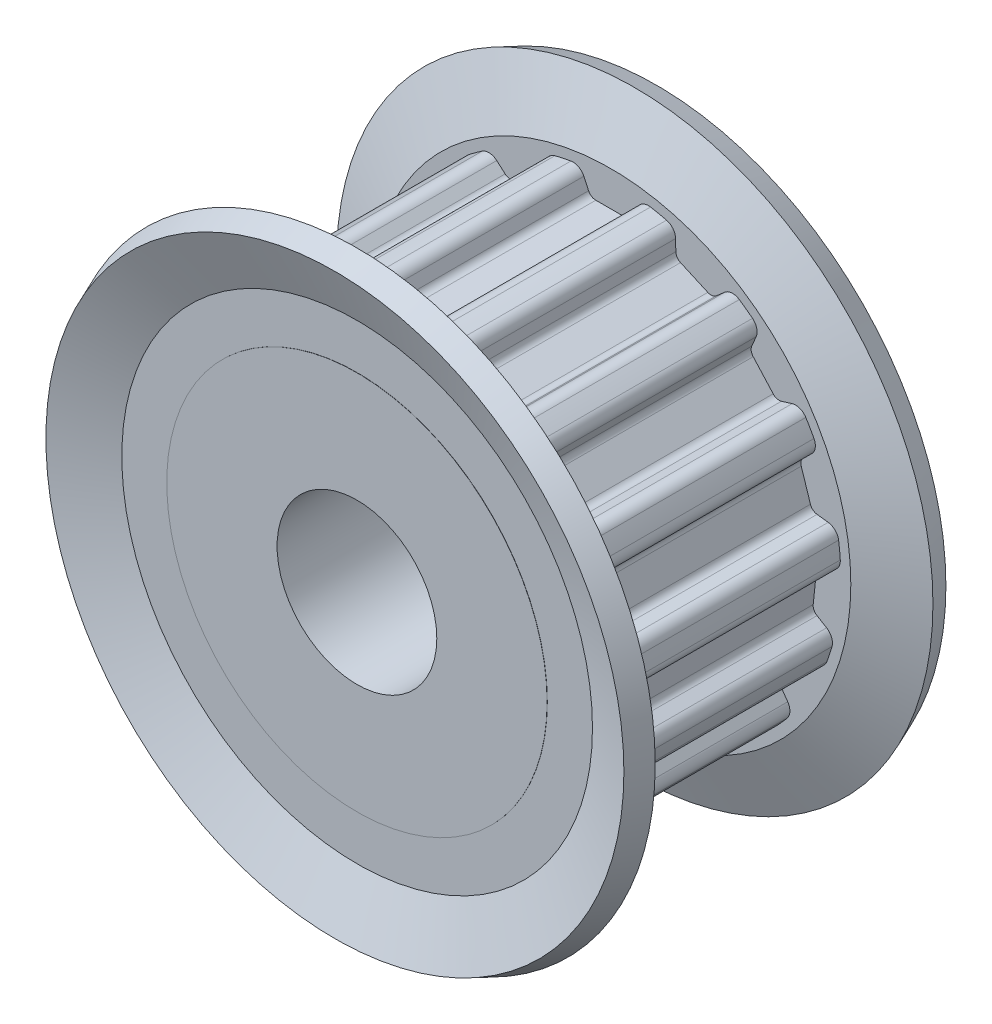
SolidWorks part; units mm, degrees
ref_plane "Front Plane" through (0, 0, 0) normal (0, 0, 1) x (1, 0, 0)
ref_plane "Top Plane" through (0, 0, 0) normal (0, 1, 0) x (1, 0, 0)
ref_plane "Right Plane" through (0, 0, 0) normal (1, 0, 0) x (0, 0, -1)
ref_axis "Axis1" through (0, 0, 73.2677) along (0, 0, -1)
sketch "SketchRevolveGearBelt01" plane through (0, 0, 0) normal (1, 0, 0) x (0, 0, -1)
  line L0 (0, 0) -> (1, 0) construction
  line L1 (6.96, 0) -> (6.96, 9.525)
  line L2 (6.96, 9.525) -> (6.95, 9.525)
  line L3 (6.95, 9.525) -> (6.95, 11.7863)
  line L4 (6.95, 11.7863) -> (8.0633, 14.4741)
  line L5 (8.0633, 14.4741) -> (6.9547, 14.9333)
  line L6 (6.9547, 14.9333) -> (5.75, 12.025)
  line L7 (5.75, 12.025) -> (5.75, 11.525)
  line L8 (5.75, 11.525) -> (-5.75, 11.525)
  line L9 (-5.75, 11.525) -> (-5.75, 12.025)
  line L10 (-5.75, 12.025) -> (-6.9547, 14.9333)
  line L11 (-6.9547, 14.9333) -> (-8.0633, 14.4741)
  line L12 (-8.0633, 14.4741) -> (-6.95, 11.7863)
  line L13 (-6.95, 11.7863) -> (-6.95, 9.525)
  line L14 (-6.95, 9.525) -> (-6.96, 9.525)
  line L15 (-6.96, 9.525) -> (-6.96, 0)
  line L16 (-6.96, 0) -> (6.96, 0)
  dimension "GearBeltSide1" = 6.96
  dimension "GearBeltFlange1OutsideWidth" = 6.95
  dimension "GearBeltFlange1OutsideLength" = 2.2613
  dimension "GearBeltFlange1X" = 1.1133
  dimension "GearBeltFlange1Y" = 2.6878
  dimension "GearBeltFlangeThickness" = 1.2
  dimension "GearBeltToothWidth1" = 5.75
  dimension "GearBeltFlangeInside" = 0.5
  dimension "GearBeltOutsideDiameter" = 11.525
  dimension "GearBeltToothWidth2" = 5.75
  dimension "GearBeltFlange2X" = 1.1133
  dimension "GearBeltFlange2OutsideWidth" = 6.95
revolve "GearBelt01" add sketch "SketchRevolveGearBelt01" angle 360 about L0
sketch "SketchToothGearBelt01" plane through (0, 0, 0) normal (0, 0, 1) x (1, 0, 0)
  line L0 (-1.3466, 11.0138) -> (-1.1098, 10.506)
  line L1 (-0.7473, 10.275) -> (0.7473, 10.275)
  line L2 (1.1098, 10.506) -> (1.3466, 11.0138)
  line L3 (1.9942, 11.3512) -> (0, 13.8912)
  line L4 (0, 13.8912) -> (-1.9942, 11.3512)
  arc A0 (-1.9942, 11.3512) -> (-1.3466, 11.0138) centre (-1.8904, 10.7602) cw
  arc A1 (-1.1098, 10.506) -> (-0.7473, 10.275) centre (-0.7473, 10.675) ccw
  arc A2 (0.7473, 10.275) -> (1.1098, 10.506) centre (0.7473, 10.675) ccw
  arc A3 (1.3466, 11.0138) -> (1.9942, 11.3512) centre (1.8904, 10.7602) cw
  dimension "GearBeltToothR1" = 1.2
  dimension "GearBeltToothR2" = 0.8
  dimension "GearBeltToothX1" = 0.2368
  dimension "GearBeltToothY1" = 0.5078
  dimension "GearBeltToothRootX" = 10.275
  dimension "GearBeltToothRootY" = 10.275
  dimension "GearBeltToothX2" = 0.2368
  dimension "GearBeltToothY2" = 0.5078
  dimension "GearBeltToothCapX1" = 1.9942
  dimension "GearBeltToothCapY1" = 2.54
  dimension "GearBeltToothCapX2" = 1.9942
  dimension "GearBeltToothCapY2" = 2.54
extrude "ToothExtrudeCutGearBelt01" cut sketch "SketchToothGearBelt01" against normal blind 5.75 and the other way blind 5.75
pattern_circular "PatternGearBelt01" count 15 every 24 about axis through (0, 0, 73.2677) along (0, 0, -1) of "ToothExtrudeCutGearBelt01"
sketch "BoreRevolveSketch" plane through (0, 0, 0) normal (1, 0, 0) x (0, 0, -1)
  line L0 (0, 0) -> (1, 0) construction
  line L1 (-6.96, 0) -> (6.96, 0)
  line L2 (6.96, 0) -> (6.96, 4)
  line L3 (6.96, 4) -> (-6.96, 4)
  line L4 (-6.96, 4) -> (-6.96, 0)
  dimension "BoreSide1" = 6.96
  dimension "TaperSide1" = 4
  dimension "BoreSide2" = 6.96
  dimension "TaperSide2" = 4
revolve "BoreRevolveCut" cut sketch "BoreRevolveSketch" angle 360 about L0
sketch "AuxiliarySketchGearBelt01" plane through (0, 0, 0) normal (0, 0, 1) x (1, 0, 0)
  circle A0 centre (0, 0) radius 12.025 construction
  dimension "PitchDiameter" = 24.05
